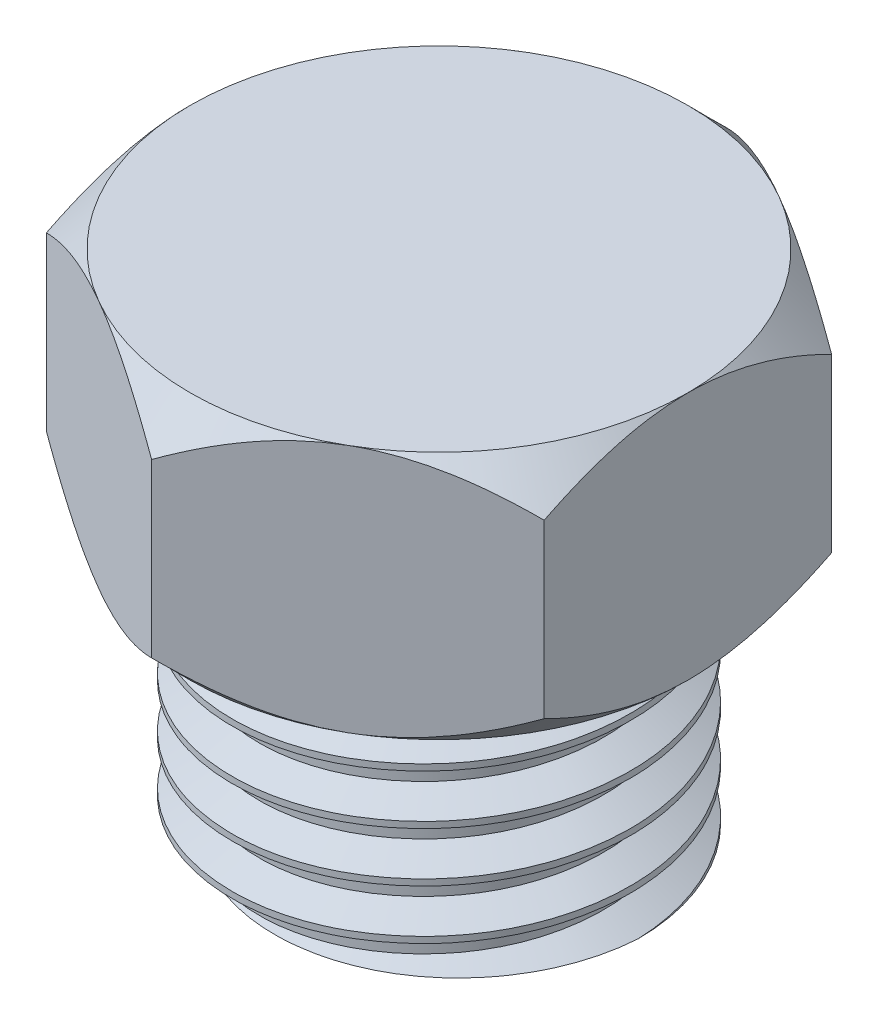
SolidWorks part; units mm, degrees
ref_plane "Alzado" through (0, 0, 0) normal (0, 0, 1) x (1, 0, 0)
ref_plane "Planta" through (0, 0, 0) normal (0, 1, 0) x (1, 0, 0)
ref_plane "Vista lateral" through (0, 0, 0) normal (1, 0, 0) x (0, 0, -1)
sketch "Croquis1" plane through (0, 0, 0) normal (0, 1, 0) x (1, 0, 0)
  line L1 (0, -5.7735) -> (5, -2.8868)
  line L2 (5, -2.8868) -> (5, 2.8868)
  line L3 (5, 2.8868) -> (0, 5.7735)
  line L4 (0, 5.7735) -> (-5, 2.8868)
  line L5 (-5, 2.8868) -> (-5, -2.8868)
  line L6 (-5, -2.8868) -> (0, -5.7735)
  circle A0 centre (0, 0) radius 5 construction
  dimension "D1" = 10
extrude "Saliente-Extruir1" add sketch "Croquis1" along normal mid plane 5
sketch "Croquis3" plane through (0, -2.5, 0) normal (0, -1, 0) x (1, 0, 0)
  circle A0 centre (0, 0) radius 4
  dimension "D1" = 8
extrude "Saliente-Extruir3" add sketch "Croquis3" along normal blind 5
sketch "Croquis4" plane through (0, -2.5, 0) normal (0, -1, 0) x (1, 0, 0)
  circle A0 centre (0, 0) radius 5
  dimension "D1" = 10
extrude "Cortar-Extruir1" cut sketch "Croquis4" against normal blind 30 draft 45 flip side to cut
mirror "Simetría1" about plane through (0, 0, 0) normal (0, 1, 0) of "Cortar-Extruir1"
thread "Rosca1" pitch 1 method cut profile "Perfil de rosca3" start angle 0, offset 1, length 0, pitch 1, diameter 8
ref_plane "Plano3" through (4, -8.5, 0) normal (0, 0, 1) x (1, 0, 0)
sketch "Perfil de rosca3" plane through (4, -8.5, 0) normal (0, 0, 1) x (1, 0, 0)
  line L0 (0, 0) -> (0, 1) construction
  line L11 (0, 0) -> (0, 0.875)
  line L12 (0, 0.875) -> (-0.5413, 0.5625)
  line L13 (-0.5413, 0.5625) -> (-0.5413, 0.3125)
  line L15 (-0.5413, 0.3125) -> (0, 0)
  line L17 (-0.5413, 0.4375) -> (0, 0.4375) construction
  point P2 (0, 0)
  dimension "Pitch" = 1
  dimension "Profile_Angle" = 60
  dimension "Profile_Land" = 0.25
  dimension "Profile_Height" = 0.5413
sketch "Croquis22" plane through (0, -7.5, 0) normal (0, -1, 0) x (1, 0, 0)
  circle A0 centre (0, 0) radius 4
